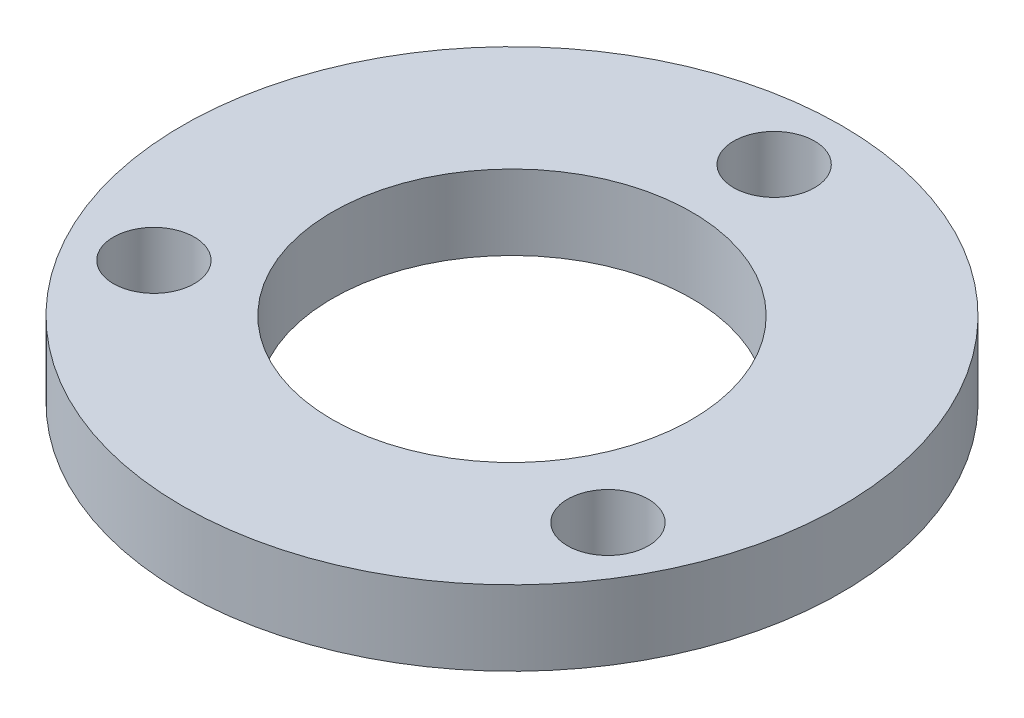
SolidWorks part; units mm, degrees
ref_plane "前视基准面" through (0, 0, 0) normal (0, 0, 1) x (1, 0, 0)
ref_plane "上视基准面" through (0, 0, 0) normal (0, 1, 0) x (1, 0, 0)
ref_plane "右视基准面" through (0, 0, 0) normal (1, 0, 0) x (0, 0, -1)
other "Configuration Table"
sketch "草图1" plane through (0, 0, 0) normal (0, 1, 0) x (1, 0, 0)
  circle A0 centre (0, 0) radius 22
  circle A1 centre (0, 0) radius 12
  circle A2 centre (0, 0) radius 17.5
  circle A3 centre (0, 17.5) radius 2.7
  dimension "D1" = 24
  dimension "D2" = 44
  dimension "D3" = 35
  dimension "D4" = 5.4
extrude "凸台-拉伸1" add sketch "草图1" along normal blind 5 contours A3 A2 A1 | A2 A3 | A2 A3 | A0 A3 A2 region at (-21.3777, 0, 0) region at (-11.0619, 0, 12.9172) region at (0, 0, -16.3174) region at (0, 0, -18.6076)
extrude "切除-拉伸1" cut sketch "草图1<3>" along normal through all both contours A2 A3 | A2 A3 region at (0, 0, -16.3174) region at (0, 0, -18.6076)
sketch "草图1<3>" plane through (0, 0, 0) normal (0, 1, 0) x (1, 0, 0) same geometry as "草图1"
pattern_circular "阵列(圆周)1" count 3 over 360 about axis through (0, 5, 0) along (0, -1, 0) of "切除-拉伸1" reverse direction yes
